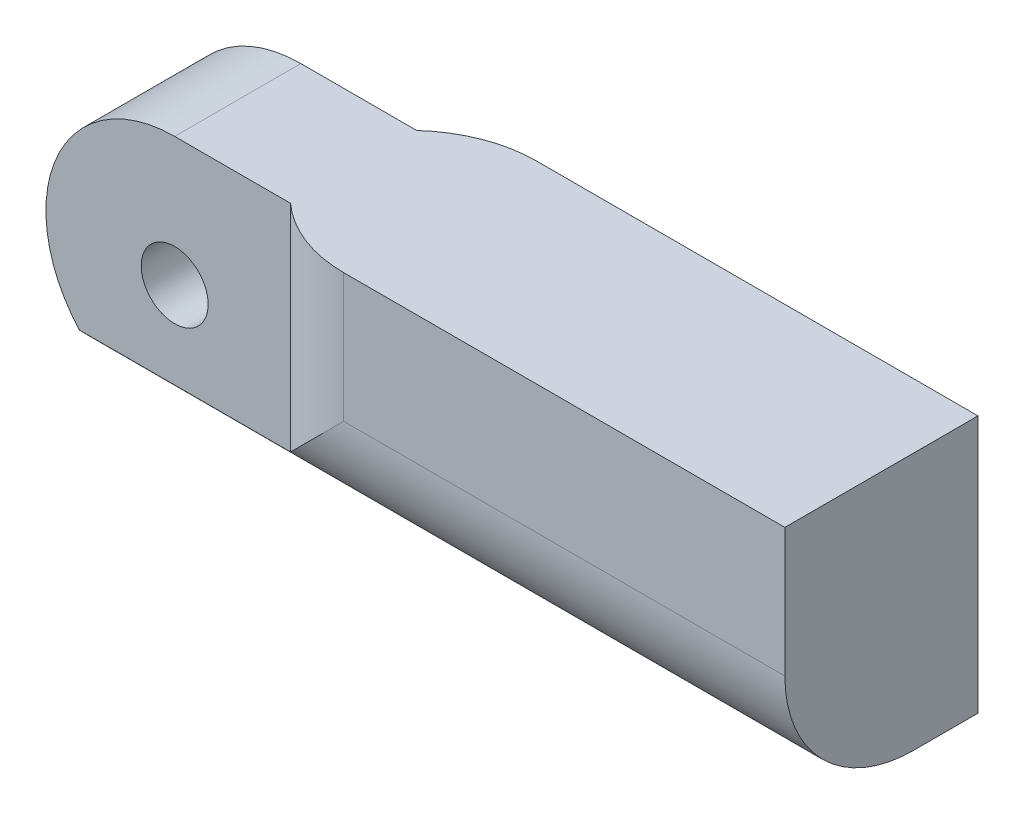
SolidWorks part; units mm, degrees
ref_plane "Front Plane" through (0, 0, 0) normal (0, 0, 1) x (1, 0, 0)
ref_plane "Top Plane" through (0, 0, 0) normal (0, 1, 0) x (1, 0, 0)
ref_plane "Right Plane" through (0, 0, 0) normal (1, 0, 0) x (0, 0, -1)
sketch "Sketch1" plane through (0, 0, 0) normal (0, 0, 1) x (1, 0, 0)
  line L0 (0, 10) -> (50, 10)
  line L1 (50, 10) -> (50, -10)
  line L2 (50, -10) -> (0, -10)
  line L3 (9, 10) -> (9, -10)
  circle A0 centre (0, 0) radius 2.6
  arc A1 (0, 10) -> (0, -10) centre (0, 0) ccw
  dimension "D1" = 5.2
  dimension "D2" = 10
  dimension "D3" = 50
  dimension "D4" = 9
extrude "Boss-Extrude1" add sketch "Sketch1" along normal mid plane 9.8 contours L0 A1 L2 L3 A0 region at (4.5, 9.7241, 0)
extrude "Boss-Extrude2" add sketch "Sketch1<3>" along normal mid plane 15 contours L0 L3 L2 L1 region at (29.5, 0, 0)
sketch "Sketch1<3>" plane through (0, 0, 0) normal (0, 0, 1) x (1, 0, 0) same geometry as "Sketch1"
fillet "Fillet1" radius 10 3 edges at (29.5, -10, 7.5) (9, 0, -7.5) (9, 0, 7.5)
